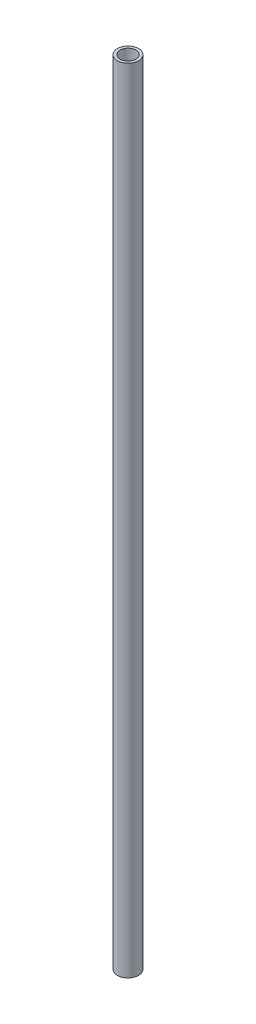
SolidWorks part; units mm, degrees
ref_plane "Front Plane" through (0, 0, 0) normal (0, 0, 1) x (1, 0, 0)
ref_plane "Top Plane" through (0, 0, 0) normal (0, 1, 0) x (1, 0, 0)
ref_plane "Right Plane" through (0, 0, 0) normal (1, 0, 0) x (0, 0, -1)
sketch "Sketch1" plane through (0, 0, 0) normal (0, 1, 0) x (1, 0, 0)
  circle A0 centre (0, 0) radius 4
  circle A1 centre (0, 0) radius 3
  dimension "D1" = 6
  dimension "D2" = 8
extrude "Boss-Extrude1" add sketch "Sketch1" along normal mid plane 175
extrude "Boss-Extrude2" add sketch "Sketch1<2>" along normal blind 125 from surface starting at face at (0, 87.5, 4)
sketch "Sketch1<2>" plane through (0, 0, 0) normal (0, 1, 0) x (1, 0, 0) same geometry as "Sketch1"
